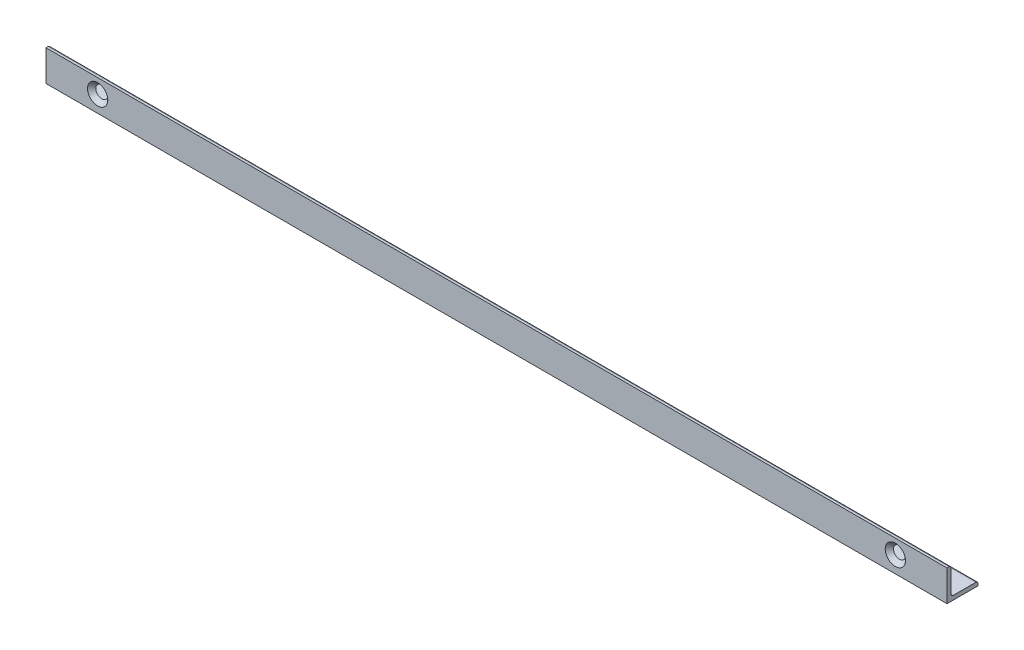
SolidWorks part; units mm, degrees
material "1060 Сплав"
ref_plane "Front" through (0, 0, 0) normal (0, 0, 1) x (1, 0, 0)
ref_plane "Top" through (0, 0, 0) normal (0, 1, 0) x (1, 0, 0)
ref_plane "Right" through (0, 0, 0) normal (1, 0, 0) x (0, 0, -1)
sketch "Эскиз1" plane through (0, 0, 0) normal (1, 0, 0) x (0, 0, -1)
  line L0 (0, 0) -> (0, 15)
  line L1 (0, 0) -> (15, 0)
  line L2 (0, 15) -> (1, 15)
  line L3 (2, 14) -> (2, 3)
  line L4 (3, 2) -> (14, 2)
  line L5 (15, 1) -> (15, 0)
  arc A0 (14, 2) -> (15, 1) centre (14, 1) cw
  arc A1 (1, 15) -> (2, 14) centre (1, 14) cw
  arc A2 (2, 3) -> (3, 2) centre (3, 3) ccw
  point P9 (15, 2)
  point P12 (2, 15)
  dimension "D5" = 1
  dimension "D1" = 15
  dimension "D2" = 15
  dimension "D3" = 2
  dimension "D4" = 2
extrude "Бобышка-Вытянуть1" add sketch "Эскиз1" along normal blind 436
sketch "Эскиз3" plane through (0, 0, -2) normal (0, 0, -1) x (-1, 0, 0)
  line L0 (-436, 3) -> (-436, 14) construction
  line L1 (-436, 15) -> (0, 15) construction
  line L2 (0, 3) -> (0, 14) construction
  circle A0 centre (-411, 8) radius 2.8
  circle A1 centre (-25, 8) radius 2.8
  dimension "D1" = 5.6
  dimension "D2" = 25
  dimension "D3" = 7
  dimension "D4" = 5.6
  dimension "D5" = 7
  dimension "D6" = 25
extrude "Вырез-Вытянуть2" cut sketch "Эскиз3" against normal through all
sketch "Эскиз4" plane through (0, 0, 0) normal (0, -1, 0) x (1, 0, 0)
  line L0 (436, -15) -> (0, -15) construction
  line L2 (436, 0) -> (436, -15) construction
  circle A0 centre (372, -9) radius 2.75
  circle A2 centre (87, -9) radius 2.75
  dimension "D1" = 5.5
  dimension "D2" = 6
  dimension "D3" = 64
  dimension "D4" = 5.5
  dimension "D5" = 282
  dimension "D6" = 6
extrude "Вырез-Вытянуть3" [suppressed] cut sketch "Эскиз4" against normal blind 2
chamfer "Фаска2" distance 2.098 angle 45 2 edges at (411, 10.8, 0) (25, 10.8, 0)
sketch "Эскиз5" [suppressed] plane through (0, 2, 0) normal (0, 1, 0) x (1, 0, 0)
  line L0 (432, 14) -> (432, 3) construction
  line L1 (432, 15) -> (0, 15) construction
  line L2 (0, 14) -> (0, 3) construction
  circle A0 centre (392, 8) radius 2.3
  circle A1 centre (40, 8) radius 2.3
  dimension "D1" = 4.6
  dimension "D2" = 40
  dimension "D3" = 7
  dimension "D4" = 4.6
  dimension "D5" = 7
  dimension "D6" = 40
extrude "Вырез-Вытянуть4" [suppressed] cut sketch "Эскиз5" against normal through all
chamfer "Фаска3" [suppressed] distance 2.05 angle 45
sketch "Эскиз6" [suppressed] plane through (432, 0, 0) normal (1, 0, 0) x (0, 0, -1)
  line L1 (15, 0) -> (2, 0)
  line L2 (15, 0) -> (15, 3)
  line L3 (15, 3) -> (2, 3)
  line L4 (2, 0) -> (2, 3)
extrude "Вырез-Вытянуть5" [suppressed] cut sketch "Эскиз6" against normal blind 15
sketch "Эскиз7" [suppressed] plane through (0, 0, 0) normal (-1, 0, 0) x (0, 0, 1)
  line L1 (-15, 0) -> (-2, 0)
  line L2 (-15, 0) -> (-15, 3)
  line L3 (-15, 3) -> (-2, 3)
  line L4 (-2, 0) -> (-2, 3)
extrude "Вырез-Вытянуть6" [suppressed] cut sketch "Эскиз7" against normal blind 15
sketch "Эскиз8" [suppressed] plane through (0, 0, -2) normal (0, 0, -1) x (-1, 0, 0)
  line L0 (0, 0) -> (0, 5)
  line L1 (0, 0) -> (0, 14) construction
  line L2 (0, 5) -> (-5, 0)
  line L3 (-15, 0) -> (0, 0) construction
  line L4 (-5, 0) -> (0, 0)
  line L5 (-432, 0) -> (-427, 0)
  line L6 (-417, 0) -> (-432, 0) construction
  line L7 (-432, 0) -> (-432, 5)
  line L8 (-432, 0) -> (-432, 14) construction
  line L9 (-432, 5) -> (-427, 0)
  dimension "D1" = 5
  dimension "D2" = 5
  dimension "D3" = 5
  dimension "D4" = 5
extrude "Вырез-Вытянуть7" [suppressed] cut sketch "Эскиз8" against normal through all
sketch "Эскиз9" [suppressed] plane through (0, 0, 0) normal (0, 0, 1) x (1, 0, 0)
  line L0 (436, 15) -> (0, 15) construction
  line L1 (436, 15) -> (436, 0) construction
  line L2 (0, 15) -> (0, 0) construction
  circle A0 centre (426, 8) radius 2.8
  circle A2 centre (10, 8) radius 2.8
  dimension "D1" = 7
  dimension "D2" = 10
  dimension "D3" = 5.6
  dimension "D4" = 7
  dimension "D5" = 10
  dimension "D6" = 5.6
extrude "Вырез-Вытянуть8" [suppressed] cut sketch "Эскиз9" against normal through all
chamfer "Фаска4" [suppressed] distance 2.098 angle 45
sketch "Эскиз10" plane through (0, 2, 0) normal (0, 1, 0) x (1, 0, 0)
  line L0 (436, 15) -> (0, 15) construction
  line L1 (436, 14) -> (436, 3) construction
  line L2 (0, 14) -> (0, 3) construction
  circle A0 centre (396, 8) radius 2.3
  circle A1 centre (40, 8) radius 2.3
  dimension "D1" = 4.6
  dimension "D2" = 7
  dimension "D3" = 40
  dimension "D4" = 4.6
  dimension "D5" = 7
  dimension "D6" = 40
extrude "Вырез-Вытянуть9" cut sketch "Эскиз10" against normal through all
chamfer "Фаска5" distance 2.05 angle 45 2 edges at (40, 0, -5.7) (396, 0, -5.7)
